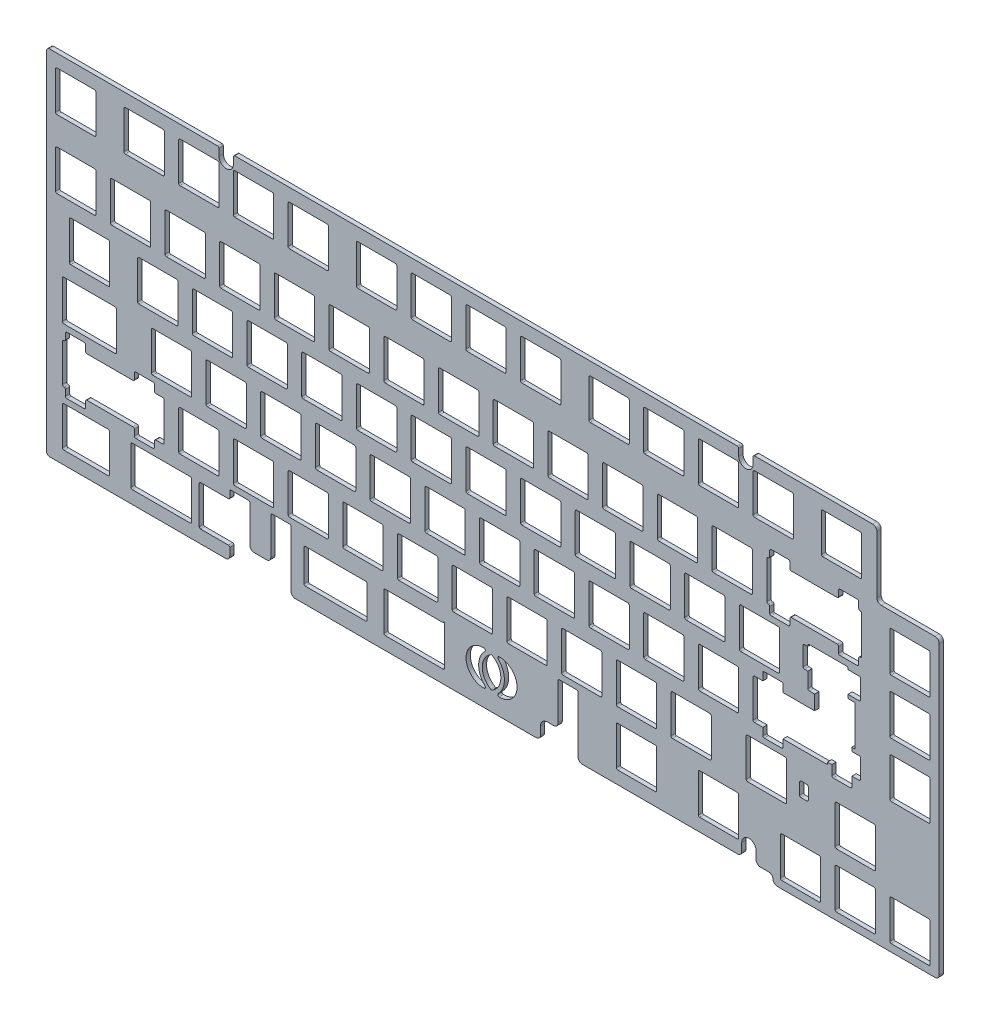
SolidWorks part; units mm, degrees
material "POM Acetal Copolymer"
ref_plane "Front Plane" through (0, 0, 0) normal (0, 0, 1) x (1, 0, 0)
ref_plane "Top Plane" through (0, 0, 0) normal (0, 1, 0) x (1, 0, 0)
ref_plane "Right Plane" through (0, 0, 0) normal (1, 0, 0) x (0, 0, -1)
sketch "Model" plane through (0, 0, 0) normal (0, 0, 1) x (1, 0, 0)
  line L0 (274.4928, 83.607) -> (287.4928, 83.607)
  line L1 (273.9928, 70.107) -> (273.9928, 75.3421)
  line L2 (8.8553, 129.8695) -> (8.8553, 63.082)
  line L3 (67.4518, 130.9695) -> (9.9553, 130.9695)
  line L4 (319.7678, 63.082) -> (319.7678, 106.4532)
  line L5 (195.4959, 7.957) -> (249.4928, 7.957)
  line L6 (86.9959, 28.958) -> (86.9959, 16.157)
  line L7 (187.4959, 29.458) -> (193.4959, 29.458)
  line L8 (193.9959, 28.958) -> (193.9959, 9.457)
  line L9 (186.9959, 16.157) -> (186.9959, 28.958)
  line L10 (87.4959, 29.458) -> (93.4959, 29.458)
  line L11 (126.357, 12.957) -> (126.357, 25.957)
  line L12 (62.0594, 12.957) -> (62.0594, 25.957)
  line L13 (38.2454, 12.957) -> (38.2454, 25.957)
  line L14 (14.4343, 12.957) -> (14.4343, 25.957)
  line L15 (72.207, 12.457) -> (62.5594, 12.457)
  line L16 (62.5594, 26.457) -> (72.207, 26.457)
  line L17 (59.3945, 25.957) -> (59.3945, 12.957)
  line L18 (58.8945, 12.457) -> (38.7454, 12.457)
  line L19 (38.7454, 26.457) -> (58.8945, 26.457)
  line L20 (30.8195, 25.957) -> (30.8195, 12.957)
  line L21 (30.3195, 12.457) -> (14.9343, 12.457)
  line L22 (14.9343, 26.457) -> (30.3195, 26.457)
  line L23 (93.9959, 28.958) -> (93.9959, 9.457)
  line L24 (146.9959, 12.457) -> (126.857, 12.457)
  line L25 (126.857, 26.457) -> (146.9959, 26.457)
  line L26 (147.4959, 26.7823) -> (147.4959, 12.957)
  line L27 (9.9553, 7.957) -> (71.207, 7.957)
  line L28 (95.4959, 7.957) -> (179.3625, 7.957)
  line L29 (263.3678, 5.0945) -> (318.2678, 5.0945)
  line L30 (180.8625, 12.157) -> (180.8625, 9.457)
  line L31 (250.9928, 12.157) -> (250.9928, 9.457)
  line L32 (255.9928, 12.157) -> (255.9928, 9.457)
  line L33 (183.3625, 14.657) -> (185.4959, 14.657)
  line L34 (81.207, 14.657) -> (85.4959, 14.657)
  line L35 (257.4928, 7.957) -> (260.371, 7.957)
  line L36 (8.8553, 63.082) -> (8.8553, 9.057)
  line L37 (319.7678, 63.082) -> (319.7678, 6.5945)
  line L38 (75.4518, 130.9695) -> (248.4268, 130.9695)
  line L39 (256.4268, 130.9695) -> (296.5553, 130.9695)
  line L40 (298.0553, 129.4695) -> (298.0553, 109.4532)
  line L41 (299.5553, 107.9532) -> (318.2678, 107.9532)
  line L42 (271.6572, 41.007) -> (273.6572, 41.007)
  line L43 (274.1572, 40.507) -> (274.1572, 36.507)
  line L44 (273.6572, 36.007) -> (271.6572, 36.007)
  line L45 (271.1572, 36.507) -> (271.1572, 40.507)
  line L46 (260.7295, 105.157) -> (260.7295, 103.157)
  line L47 (268.2295, 102.657) -> (284.2295, 102.657)
  line L48 (268.2295, 88.657) -> (284.2295, 88.657)
  line L49 (261.2295, 105.657) -> (267.2295, 105.657)
  line L50 (261.2295, 85.657) -> (267.2295, 85.657)
  line L51 (267.7295, 103.157) -> (267.7295, 105.157)
  line L52 (267.7295, 88.157) -> (267.7295, 86.157)
  line L53 (291.7295, 105.157) -> (291.7295, 103.157)
  line L54 (291.2295, 105.657) -> (285.2295, 105.657)
  line L55 (291.2295, 85.657) -> (285.2295, 85.657)
  line L56 (284.7295, 103.157) -> (284.7295, 105.157)
  line L57 (284.7295, 88.157) -> (284.7295, 86.157)
  line L58 (258.3508, 50.557) -> (258.3508, 48.057)
  line L59 (265.3508, 50.557) -> (280.8516, 50.557)
  line L60 (258.8508, 67.557) -> (264.8508, 67.557)
  line L61 (258.8508, 47.557) -> (264.8508, 47.557)
  line L62 (265.3508, 64.557) -> (265.3508, 67.057)
  line L63 (265.3508, 50.557) -> (265.3508, 48.057)
  line L64 (288.8508, 47.557) -> (282.8508, 47.557)
  line L65 (282.3508, 51.3421) -> (282.3508, 48.057)
  line L66 (15.4632, 48.0073) -> (15.4632, 46.007)
  line L67 (22.9632, 45.5073) -> (38.9632, 45.5073)
  line L68 (22.9632, 31.5073) -> (38.9632, 31.5073)
  line L69 (15.9632, 48.5073) -> (21.9632, 48.5073)
  line L70 (15.9632, 28.5073) -> (21.9632, 28.5073)
  line L71 (22.4632, 46.0073) -> (22.4632, 48.0073)
  line L72 (22.4632, 31.0073) -> (22.4632, 29.0073)
  line L73 (46.4632, 48.0073) -> (46.4632, 46.007)
  line L74 (45.9632, 48.5073) -> (39.9632, 48.5073)
  line L75 (45.9632, 28.5073) -> (39.9632, 28.5073)
  line L76 (39.4632, 46.0073) -> (39.4632, 48.0073)
  line L77 (39.4632, 31.0073) -> (39.4632, 29.0073)
  line L78 (258.3508, 50.557) -> (255.4453, 50.557)
  line L79 (276.3765, 69.607) -> (274.4928, 69.607)
  line L80 (276.3765, 64.557) -> (276.3765, 69.607)
  line L81 (292.3508, 82.2801) -> (292.3508, 75.8421)
  line L82 (292.3508, 58.2801) -> (292.3508, 51.8421)
  line L83 (291.8508, 82.7801) -> (287.9953, 82.7801)
  line L84 (255.4453, 64.557) -> (258.3508, 64.557)
  line L85 (290.3765, 74.0611) -> (290.3765, 60.0611)
  line L86 (254.9453, 64.057) -> (254.9453, 51.057)
  line L87 (287.9953, 75.3421) -> (291.8508, 75.3421)
  line L88 (289.3508, 58.7801) -> (291.8508, 58.7801)
  line L89 (290.3765, 74.0611) -> (287.9953, 74.0611)
  line L90 (287.9953, 74.0611) -> (287.9953, 75.3421)
  line L91 (289.3508, 58.7801) -> (289.3508, 60.0611)
  line L92 (289.3508, 60.0611) -> (290.3765, 60.0611)
  line L93 (282.3508, 51.3421) -> (280.8516, 51.3421)
  line L94 (280.8516, 51.3421) -> (280.8516, 50.557)
  line L95 (258.3508, 67.057) -> (258.3508, 64.557)
  line L96 (289.3508, 48.057) -> (289.3508, 51.3421)
  line L97 (291.8508, 51.3421) -> (289.3508, 51.3421)
  line L98 (287.9928, 83.107) -> (287.9953, 82.7801)
  line L99 (265.3508, 64.557) -> (276.3765, 64.557)
  line L100 (272.3508, 82.2801) -> (272.3508, 75.8421)
  line L101 (272.8508, 82.7801) -> (273.9928, 82.7801)
  line L102 (273.9928, 75.3421) -> (272.8508, 75.3421)
  line L103 (273.9928, 82.7801) -> (273.9928, 83.107)
  line L104 (259.7053, 89.157) -> (259.7053, 102.157)
  line L105 (292.7553, 102.157) -> (292.7553, 89.157)
  line L106 (291.7295, 86.157) -> (291.7295, 88.157)
  line L107 (292.2295, 88.657) -> (292.2553, 88.657)
  line L108 (292.2295, 102.657) -> (292.2553, 102.657)
  line L109 (260.2053, 102.657) -> (260.2295, 102.657)
  line L110 (260.7295, 86.157) -> (260.7295, 88.157)
  line L111 (260.2295, 88.657) -> (260.2053, 88.657)
  line L112 (49.8678, 45.007) -> (49.8678, 32.007)
  line L113 (46.4632, 29.0073) -> (46.4632, 31.007)
  line L114 (46.9632, 31.507) -> (49.3678, 31.507)
  line L115 (46.9632, 45.507) -> (49.3678, 45.507)
  line L116 (14.4365, 32.007) -> (14.4365, 45.007)
  line L117 (15.4632, 29.0073) -> (15.4632, 31.007)
  line L118 (14.9632, 31.507) -> (14.9365, 31.507)
  line L119 (14.9365, 45.507) -> (14.9632, 45.507)
  line L120 (79.707, 28.958) -> (79.707, 16.157)
  line L121 (72.707, 11.957) -> (72.707, 9.457)
  line L122 (72.707, 26.957) -> (72.707, 28.958)
  line L123 (73.207, 29.458) -> (79.207, 29.458)
  line L124 (120.5413, 13.957) -> (120.5413, 24.957)
  line L125 (99.0413, 13.457) -> (120.0413, 13.457)
  line L126 (98.5413, 24.957) -> (98.5413, 13.957)
  line L127 (120.0413, 25.457) -> (99.0413, 25.457)
  line L144 (12.5303, 112.4445) -> (25.5803, 112.4445)
  line L145 (26.0803, 112.9445) -> (26.0803, 125.9945)
  line L146 (25.5803, 126.4945) -> (12.5303, 126.4945)
  line L147 (12.0303, 125.9945) -> (12.0303, 112.9445)
  line L148 (36.3428, 112.4445) -> (49.3928, 112.4445)
  line L149 (49.8928, 112.9445) -> (49.8928, 125.9945)
  line L150 (49.3928, 126.4945) -> (36.3428, 126.4945)
  line L151 (35.8428, 125.9945) -> (35.8428, 112.9445)
  line L152 (93.4928, 112.4445) -> (106.5428, 112.4445)
  line L153 (107.0428, 112.9445) -> (107.0428, 125.9945)
  line L154 (106.5428, 126.4945) -> (93.4928, 126.4945)
  line L155 (92.9928, 125.9945) -> (92.9928, 112.9445)
  line L156 (117.3053, 112.4445) -> (130.3553, 112.4445)
  line L157 (130.8553, 112.9445) -> (130.8553, 125.9945)
  line L158 (130.3553, 126.4945) -> (117.3053, 126.4945)
  line L159 (116.8053, 125.9945) -> (116.8053, 112.9445)
  line L160 (136.3553, 112.4445) -> (149.4053, 112.4445)
  line L161 (149.9053, 112.9445) -> (149.9053, 125.9945)
  line L162 (149.4053, 126.4945) -> (136.3553, 126.4945)
  line L163 (135.8553, 125.9945) -> (135.8553, 112.9445)
  line L164 (155.4053, 112.4445) -> (168.4553, 112.4445)
  line L165 (168.9553, 112.9445) -> (168.9553, 125.9945)
  line L166 (168.4553, 126.4945) -> (155.4053, 126.4945)
  line L167 (154.9053, 125.9945) -> (154.9053, 112.9445)
  line L168 (174.4553, 112.4445) -> (187.5053, 112.4445)
  line L169 (188.0053, 112.9445) -> (188.0053, 125.9945)
  line L170 (187.5053, 126.4945) -> (174.4553, 126.4945)
  line L171 (173.9553, 125.9945) -> (173.9553, 112.9445)
  line L172 (198.2678, 112.4445) -> (211.3178, 112.4445)
  line L173 (211.8178, 112.9445) -> (211.8178, 125.9945)
  line L174 (211.3178, 126.4945) -> (198.2678, 126.4945)
  line L175 (197.7678, 125.9945) -> (197.7678, 112.9445)
  line L176 (217.3178, 112.4445) -> (230.3678, 112.4445)
  line L177 (230.8678, 112.9445) -> (230.8678, 125.9945)
  line L178 (230.3678, 126.4945) -> (217.3178, 126.4945)
  line L179 (216.8178, 125.9945) -> (216.8178, 112.9445)
  line L180 (279.2303, 112.4445) -> (292.2803, 112.4445)
  line L181 (292.7803, 112.9445) -> (292.7803, 125.9945)
  line L182 (292.2803, 126.4945) -> (279.2303, 126.4945)
  line L183 (278.7303, 125.9945) -> (278.7303, 112.9445)
  line L184 (303.0428, 88.632) -> (316.0928, 88.632)
  line L185 (316.5928, 89.132) -> (316.5928, 102.182)
  line L186 (316.0928, 102.682) -> (303.0428, 102.682)
  line L187 (302.5428, 102.182) -> (302.5428, 89.132)
  line L188 (283.9928, 26.7195) -> (297.0428, 26.7195)
  line L189 (297.5428, 27.2195) -> (297.5428, 40.2695)
  line L190 (297.0428, 40.7695) -> (283.9928, 40.7695)
  line L191 (283.4928, 40.2695) -> (283.4928, 27.2195)
  line L192 (303.0428, 7.6695) -> (316.0928, 7.6695)
  line L193 (316.5928, 8.1695) -> (316.5928, 21.2195)
  line L194 (316.0928, 21.7195) -> (303.0428, 21.7195)
  line L195 (302.5428, 21.2195) -> (302.5428, 8.1695)
  line L196 (283.9928, 7.6695) -> (297.0428, 7.6695)
  line L197 (297.5428, 8.1695) -> (297.5428, 21.2195)
  line L198 (297.0428, 21.7195) -> (283.9928, 21.7195)
  line L199 (283.4928, 21.2195) -> (283.4928, 8.1695)
  line L200 (264.9428, 7.6695) -> (277.9928, 7.6695)
  line L201 (278.4928, 8.1695) -> (278.4928, 21.2195)
  line L202 (277.9928, 21.7195) -> (264.9428, 21.7195)
  line L203 (264.4428, 21.2195) -> (264.4428, 8.1695)
  line L204 (236.3678, 12.432) -> (249.4178, 12.432)
  line L205 (249.9178, 12.932) -> (249.9178, 25.982)
  line L206 (249.4178, 26.482) -> (236.3678, 26.482)
  line L207 (235.8678, 25.982) -> (235.8678, 12.932)
  line L208 (207.7928, 12.432) -> (220.8428, 12.432)
  line L209 (221.3428, 12.932) -> (221.3428, 25.982)
  line L210 (220.8428, 26.482) -> (207.7928, 26.482)
  line L211 (207.2928, 25.982) -> (207.2928, 12.932)
  line L212 (253.0365, 31.482) -> (266.0865, 31.482)
  line L213 (266.5865, 31.982) -> (266.5865, 45.032)
  line L214 (266.0865, 45.532) -> (253.0365, 45.532)
  line L215 (252.5365, 45.032) -> (252.5365, 31.982)
  line L216 (226.8428, 31.482) -> (239.8928, 31.482)
  line L217 (240.3928, 31.982) -> (240.3928, 45.032)
  line L218 (239.8928, 45.532) -> (226.8428, 45.532)
  line L219 (226.3428, 45.032) -> (226.3428, 31.982)
  line L220 (207.7928, 31.482) -> (220.8428, 31.482)
  line L221 (221.3428, 31.982) -> (221.3428, 45.032)
  line L222 (220.8428, 45.532) -> (207.7928, 45.532)
  line L223 (207.2928, 45.032) -> (207.2928, 31.982)
  line L224 (188.7428, 31.482) -> (201.7928, 31.482)
  line L225 (202.2928, 31.982) -> (202.2928, 45.032)
  line L226 (201.7928, 45.532) -> (188.7428, 45.532)
  line L227 (188.2428, 45.032) -> (188.2428, 31.982)
  line L228 (169.6928, 31.482) -> (182.7428, 31.482)
  line L229 (183.2428, 31.982) -> (183.2428, 45.032)
  line L230 (182.7428, 45.532) -> (169.6928, 45.532)
  line L231 (169.1928, 45.032) -> (169.1928, 31.982)
  line L232 (150.6428, 31.482) -> (163.6928, 31.482)
  line L233 (164.1928, 31.982) -> (164.1928, 45.032)
  line L234 (163.6928, 45.532) -> (150.6428, 45.532)
  line L235 (150.1428, 45.032) -> (150.1428, 31.982)
  line L236 (131.5928, 31.482) -> (144.6428, 31.482)
  line L237 (145.1428, 31.982) -> (145.1428, 45.032)
  line L238 (144.6428, 45.532) -> (131.5928, 45.532)
  line L239 (131.0928, 45.032) -> (131.0928, 31.982)
  line L240 (112.5428, 31.482) -> (125.5928, 31.482)
  line L241 (126.0928, 31.982) -> (126.0928, 45.032)
  line L242 (125.5928, 45.532) -> (112.5428, 45.532)
  line L243 (112.0428, 45.032) -> (112.0428, 31.982)
  line L244 (93.4928, 31.482) -> (106.5428, 31.482)
  line L245 (107.0428, 31.982) -> (107.0428, 45.032)
  line L246 (106.5428, 45.532) -> (93.4928, 45.532)
  line L247 (92.9928, 45.032) -> (92.9928, 31.982)
  line L248 (74.4428, 31.482) -> (87.4928, 31.482)
  line L249 (87.9928, 31.982) -> (87.9928, 45.032)
  line L250 (87.4928, 45.532) -> (74.4428, 45.532)
  line L251 (73.9428, 45.032) -> (73.9428, 31.982)
  line L252 (55.3928, 31.482) -> (68.4428, 31.482)
  line L253 (68.9428, 31.982) -> (68.9428, 45.032)
  line L254 (68.4428, 45.532) -> (55.3928, 45.532)
  line L255 (54.8928, 45.032) -> (54.8928, 31.982)
  line L256 (45.8678, 50.532) -> (58.9178, 50.532)
  line L257 (59.4178, 51.032) -> (59.4178, 64.082)
  line L258 (58.9178, 64.582) -> (45.8678, 64.582)
  line L259 (45.3678, 64.082) -> (45.3678, 51.032)
  line L260 (64.9178, 50.532) -> (77.9678, 50.532)
  line L261 (78.4678, 51.032) -> (78.4678, 64.082)
  line L262 (77.9678, 64.582) -> (64.9178, 64.582)
  line L263 (64.4178, 64.082) -> (64.4178, 51.032)
  line L264 (83.9678, 50.532) -> (97.0178, 50.532)
  line L265 (97.5178, 51.032) -> (97.5178, 64.082)
  line L266 (97.0178, 64.582) -> (83.9678, 64.582)
  line L267 (83.4678, 64.082) -> (83.4678, 51.032)
  line L268 (103.0178, 50.532) -> (116.0678, 50.532)
  line L269 (116.5678, 51.032) -> (116.5678, 64.082)
  line L270 (116.0678, 64.582) -> (103.0178, 64.582)
  line L271 (102.5178, 64.082) -> (102.5178, 51.032)
  line L272 (122.0678, 50.532) -> (135.1178, 50.532)
  line L273 (135.6178, 51.032) -> (135.6178, 64.082)
  line L274 (135.1178, 64.582) -> (122.0678, 64.582)
  line L275 (121.5678, 64.082) -> (121.5678, 51.032)
  line L276 (141.1178, 50.532) -> (154.1678, 50.532)
  line L277 (154.6678, 51.032) -> (154.6678, 64.082)
  line L278 (154.1678, 64.582) -> (141.1178, 64.582)
  line L279 (140.6178, 64.082) -> (140.6178, 51.032)
  line L280 (160.1678, 50.532) -> (173.2178, 50.532)
  line L281 (173.7178, 51.032) -> (173.7178, 64.082)
  line L282 (173.2178, 64.582) -> (160.1678, 64.582)
  line L283 (159.6678, 64.082) -> (159.6678, 51.032)
  line L284 (179.2178, 50.532) -> (192.2678, 50.532)
  line L285 (192.7678, 51.032) -> (192.7678, 64.082)
  line L286 (192.2678, 64.582) -> (179.2178, 64.582)
  line L287 (178.7178, 64.082) -> (178.7178, 51.032)
  line L288 (198.2678, 50.532) -> (211.3178, 50.532)
  line L289 (211.8178, 51.032) -> (211.8178, 64.082)
  line L290 (211.3178, 64.582) -> (198.2678, 64.582)
  line L291 (197.7678, 64.082) -> (197.7678, 51.032)
  line L292 (217.3178, 50.532) -> (230.3678, 50.532)
  line L293 (230.8678, 51.032) -> (230.8678, 64.082)
  line L294 (230.3678, 64.582) -> (217.3178, 64.582)
  line L295 (216.8178, 64.082) -> (216.8178, 51.032)
  line L296 (236.3678, 50.532) -> (249.4178, 50.532)
  line L297 (249.9178, 51.032) -> (249.9178, 64.082)
  line L298 (249.4178, 64.582) -> (236.3678, 64.582)
  line L299 (235.8678, 64.082) -> (235.8678, 51.032)
  line L300 (17.2928, 69.582) -> (30.3428, 69.582)
  line L301 (30.8428, 70.082) -> (30.8428, 83.132)
  line L302 (30.3428, 83.632) -> (17.2928, 83.632)
  line L303 (16.7928, 83.132) -> (16.7928, 70.082)
  line L304 (12.5303, 88.632) -> (25.5803, 88.632)
  line L305 (26.0803, 89.132) -> (26.0803, 102.182)
  line L306 (25.5803, 102.682) -> (12.5303, 102.682)
  line L307 (12.0303, 102.182) -> (12.0303, 89.132)
  line L308 (31.5803, 88.632) -> (44.6303, 88.632)
  line L309 (45.1303, 89.132) -> (45.1303, 102.182)
  line L310 (44.6303, 102.682) -> (31.5803, 102.682)
  line L311 (31.0803, 102.182) -> (31.0803, 89.132)
  line L312 (50.6303, 88.632) -> (63.6803, 88.632)
  line L313 (64.1803, 89.132) -> (64.1803, 102.182)
  line L314 (63.6803, 102.682) -> (50.6303, 102.682)
  line L315 (50.1303, 102.182) -> (50.1303, 89.132)
  line L316 (69.6803, 88.632) -> (82.7303, 88.632)
  line L317 (83.2303, 89.132) -> (83.2303, 102.182)
  line L318 (82.7303, 102.682) -> (69.6803, 102.682)
  line L319 (69.1803, 102.182) -> (69.1803, 89.132)
  line L320 (88.7303, 88.632) -> (101.7803, 88.632)
  line L321 (102.2803, 89.132) -> (102.2803, 102.182)
  line L322 (101.7803, 102.682) -> (88.7303, 102.682)
  line L323 (88.2303, 102.182) -> (88.2303, 89.132)
  line L324 (107.7803, 88.632) -> (120.8303, 88.632)
  line L325 (121.3303, 89.132) -> (121.3303, 102.182)
  line L326 (120.8303, 102.682) -> (107.7803, 102.682)
  line L327 (107.2803, 102.182) -> (107.2803, 89.132)
  line L328 (126.8303, 88.632) -> (139.8803, 88.632)
  line L329 (140.3803, 89.132) -> (140.3803, 102.182)
  line L330 (139.8803, 102.682) -> (126.8303, 102.682)
  line L331 (126.3303, 102.182) -> (126.3303, 89.132)
  line L332 (145.8803, 88.632) -> (158.9303, 88.632)
  line L333 (159.4303, 89.132) -> (159.4303, 102.182)
  line L334 (158.9303, 102.682) -> (145.8803, 102.682)
  line L335 (145.3803, 102.182) -> (145.3803, 89.132)
  line L336 (164.9303, 88.632) -> (177.9803, 88.632)
  line L337 (178.4803, 89.132) -> (178.4803, 102.182)
  line L338 (177.9803, 102.682) -> (164.9303, 102.682)
  line L339 (164.4303, 102.182) -> (164.4303, 89.132)
  line L340 (183.9803, 88.632) -> (197.0303, 88.632)
  line L341 (197.5303, 89.132) -> (197.5303, 102.182)
  line L342 (197.0303, 102.682) -> (183.9803, 102.682)
  line L343 (183.4803, 102.182) -> (183.4803, 89.132)
  line L344 (203.0303, 88.632) -> (216.0803, 88.632)
  line L345 (216.5803, 89.132) -> (216.5803, 102.182)
  line L346 (216.0803, 102.682) -> (203.0303, 102.682)
  line L347 (202.5303, 102.182) -> (202.5303, 89.132)
  line L348 (222.0803, 88.632) -> (235.1303, 88.632)
  line L349 (235.6303, 89.132) -> (235.6303, 102.182)
  line L350 (235.1303, 102.682) -> (222.0803, 102.682)
  line L351 (221.5803, 102.182) -> (221.5803, 89.132)
  line L352 (241.1303, 88.632) -> (254.1803, 88.632)
  line L353 (254.6803, 89.132) -> (254.6803, 102.182)
  line L354 (254.1803, 102.682) -> (241.1303, 102.682)
  line L355 (240.6303, 102.182) -> (240.6303, 89.132)
  line L356 (41.1053, 69.582) -> (54.1553, 69.582)
  line L357 (54.6553, 70.082) -> (54.6553, 83.132)
  line L358 (54.1553, 83.632) -> (41.1053, 83.632)
  line L359 (40.6053, 83.132) -> (40.6053, 70.082)
  line L360 (60.1553, 69.582) -> (73.2053, 69.582)
  line L361 (73.7053, 70.082) -> (73.7053, 83.132)
  line L362 (73.2053, 83.632) -> (60.1553, 83.632)
  line L363 (59.6553, 83.132) -> (59.6553, 70.082)
  line L364 (79.2053, 69.582) -> (92.2553, 69.582)
  line L365 (92.7553, 70.082) -> (92.7553, 83.132)
  line L366 (92.2553, 83.632) -> (79.2053, 83.632)
  line L367 (78.7053, 83.132) -> (78.7053, 70.082)
  line L368 (98.2553, 69.582) -> (111.3053, 69.582)
  line L369 (111.8053, 70.082) -> (111.8053, 83.132)
  line L370 (111.3053, 83.632) -> (98.2553, 83.632)
  line L371 (97.7553, 83.132) -> (97.7553, 70.082)
  line L372 (117.3053, 69.582) -> (130.3553, 69.582)
  line L373 (130.8553, 70.082) -> (130.8553, 83.132)
  line L374 (130.3553, 83.632) -> (117.3053, 83.632)
  line L375 (116.8053, 83.132) -> (116.8053, 70.082)
  line L376 (136.3553, 69.582) -> (149.4053, 69.582)
  line L377 (149.9053, 70.082) -> (149.9053, 83.132)
  line L378 (149.4053, 83.632) -> (136.3553, 83.632)
  line L379 (135.8553, 83.132) -> (135.8553, 70.082)
  line L380 (155.4053, 69.582) -> (168.4553, 69.582)
  line L381 (168.9553, 70.082) -> (168.9553, 83.132)
  line L382 (168.4553, 83.632) -> (155.4053, 83.632)
  line L383 (154.9053, 83.132) -> (154.9053, 70.082)
  line L384 (174.4553, 69.582) -> (187.5053, 69.582)
  line L385 (188.0053, 70.082) -> (188.0053, 83.132)
  line L386 (187.5053, 83.632) -> (174.4553, 83.632)
  line L387 (173.9553, 83.132) -> (173.9553, 70.082)
  line L388 (193.5053, 69.582) -> (206.5553, 69.582)
  line L389 (207.0553, 70.082) -> (207.0553, 83.132)
  line L390 (206.5553, 83.632) -> (193.5053, 83.632)
  line L391 (193.0053, 83.132) -> (193.0053, 70.082)
  line L392 (212.5553, 69.582) -> (225.6053, 69.582)
  line L393 (226.1053, 70.082) -> (226.1053, 83.132)
  line L394 (225.6053, 83.632) -> (212.5553, 83.632)
  line L395 (212.0553, 83.132) -> (212.0553, 70.082)
  line L396 (231.6053, 69.582) -> (244.6553, 69.582)
  line L397 (245.1553, 70.082) -> (245.1553, 83.132)
  line L398 (244.6553, 83.632) -> (231.6053, 83.632)
  line L399 (231.1053, 83.132) -> (231.1053, 70.082)
  line L400 (250.6553, 69.582) -> (263.7053, 69.582)
  line L401 (264.2053, 70.082) -> (264.2053, 83.132)
  line L402 (263.7053, 83.632) -> (250.6553, 83.632)
  line L403 (250.1553, 83.132) -> (250.1553, 70.082)
  line L404 (303.0428, 69.582) -> (316.0928, 69.582)
  line L405 (316.5928, 70.082) -> (316.5928, 83.132)
  line L406 (316.0928, 83.632) -> (303.0428, 83.632)
  line L407 (302.5428, 83.132) -> (302.5428, 70.082)
  line L408 (303.0678, 64.582) -> (316.1178, 64.582)
  line L409 (302.5428, 51.057) -> (302.5428, 64.057)
  line L410 (316.0678, 50.532) -> (303.0678, 50.532)
  line L411 (316.5928, 64.107) -> (316.5928, 51.057)
  line L412 (32.699, 50.507) -> (14.9365, 50.507)
  line L413 (33.249, 64.057) -> (33.249, 51.057)
  line L414 (14.9365, 64.607) -> (32.699, 64.607)
  line L415 (14.3865, 51.057) -> (14.3865, 64.057)
  line L416 (236.3678, 112.4445) -> (249.4178, 112.4445)
  line L417 (249.9178, 112.9445) -> (249.9178, 125.9945)
  line L418 (249.4178, 126.4945) -> (236.3678, 126.4945)
  line L419 (235.8678, 125.9945) -> (235.8678, 112.9445)
  line L420 (255.4178, 112.4445) -> (268.4678, 112.4445)
  line L421 (268.9678, 112.9445) -> (268.9678, 125.9945)
  line L422 (268.4678, 126.4945) -> (255.4178, 126.4945)
  line L423 (254.9178, 125.9945) -> (254.9178, 112.9445)
  line L424 (55.3928, 112.4445) -> (68.4428, 112.4445)
  line L425 (68.9428, 112.9445) -> (68.9428, 125.9945)
  line L426 (68.4428, 126.4945) -> (55.3928, 126.4945)
  line L427 (54.8928, 125.9945) -> (54.8928, 112.9445)
  line L428 (74.4428, 112.4445) -> (87.4928, 112.4445)
  line L429 (87.9928, 112.9445) -> (87.9928, 125.9945)
  line L430 (87.4928, 126.4945) -> (74.4428, 126.4945)
  line L431 (73.9428, 125.9945) -> (73.9428, 112.9445)
  line L432 (67.4518, 130.9695) -> (75.4518, 130.9695)
  line L433 (248.4268, 130.9695) -> (256.4268, 130.9695)
  arc A0 (319.7678, 106.4532) -> (318.2678, 107.9532) centre (318.2678, 106.4532) ccw
  arc A1 (318.2678, 5.0945) -> (319.7678, 6.5945) centre (318.2678, 6.5945) ccw
  arc A2 (193.9959, 9.457) -> (195.4959, 7.957) centre (195.4959, 9.457) ccw
  arc A3 (273.9928, 70.107) -> (274.4928, 69.607) centre (274.4928, 70.107) ccw
  arc A4 (287.9928, 83.107) -> (287.4928, 83.607) centre (287.4928, 83.107) ccw
  arc A5 (274.4928, 83.607) -> (273.9928, 83.107) centre (274.4928, 83.107) ccw
  arc A6 (8.8553, 9.057) -> (9.9553, 7.957) centre (9.9553, 9.057) ccw
  arc A7 (9.9553, 130.9695) -> (8.8553, 129.8695) centre (9.9553, 129.8695) ccw
  arc A8 (85.4959, 14.657) -> (86.9959, 16.157) centre (85.4959, 16.157) ccw
  arc A9 (193.9959, 28.958) -> (193.4959, 29.458) centre (193.4959, 28.958) ccw
  arc A10 (187.4959, 29.458) -> (186.9959, 28.958) centre (187.4959, 28.958) ccw
  arc A11 (185.4959, 14.657) -> (186.9959, 16.157) centre (185.4959, 16.157) ccw
  arc A12 (87.4959, 29.458) -> (86.9959, 28.958) centre (87.4959, 28.958) ccw
  arc A13 (126.357, 12.957) -> (126.857, 12.457) centre (126.857, 12.957) ccw
  arc A14 (93.9959, 28.958) -> (93.4959, 29.458) centre (93.4959, 28.958) ccw
  arc A15 (38.7454, 26.457) -> (38.2454, 25.957) centre (38.7454, 25.957) ccw
  arc A16 (14.9343, 26.457) -> (14.4343, 25.957) centre (14.9343, 25.957) ccw
  arc A17 (62.0594, 12.957) -> (62.5594, 12.457) centre (62.5594, 12.957) ccw
  arc A18 (62.5594, 26.457) -> (62.0594, 25.957) centre (62.5594, 25.957) ccw
  arc A19 (38.2454, 12.957) -> (38.7454, 12.457) centre (38.7454, 12.957) ccw
  arc A20 (58.8945, 12.457) -> (59.3945, 12.957) centre (58.8945, 12.957) ccw
  arc A21 (59.3945, 25.957) -> (58.8945, 26.457) centre (58.8945, 25.957) ccw
  arc A22 (30.3195, 12.457) -> (30.8195, 12.957) centre (30.3195, 12.957) ccw
  arc A23 (14.4343, 12.957) -> (14.9343, 12.457) centre (14.9343, 12.957) ccw
  arc A24 (30.8195, 25.957) -> (30.3195, 26.457) centre (30.3195, 25.957) ccw
  arc A25 (126.857, 26.457) -> (126.357, 25.957) centre (126.857, 25.957) ccw
  arc A26 (146.9959, 12.457) -> (147.4959, 12.957) centre (146.9959, 12.957) ccw
  arc A27 (147.4959, 26.7823) -> (146.9959, 26.457) centre (147.4647, 26.2833) ccw
  arc A28 (93.9959, 9.457) -> (95.4959, 7.957) centre (95.4959, 9.457) ccw
  arc A29 (261.8694, 6.5258) -> (263.3678, 5.0945) centre (263.3678, 6.5945) ccw
  arc A30 (261.8694, 6.5258) -> (260.371, 7.957) centre (260.371, 6.457) ccw
  arc A31 (179.3625, 7.957) -> (180.8625, 9.457) centre (179.3625, 9.457) ccw
  arc A32 (255.9928, 9.457) -> (257.4928, 7.957) centre (257.4928, 9.457) ccw
  arc A33 (249.4928, 7.957) -> (250.9928, 9.457) centre (249.4928, 9.457) ccw
  arc A34 (255.9928, 12.157) -> (250.9928, 12.157) centre (253.4928, 12.157) ccw
  arc A35 (183.3625, 14.657) -> (180.8625, 12.157) centre (183.3625, 12.157) ccw
  arc A36 (298.0553, 129.4695) -> (296.5553, 130.9695) centre (296.5553, 129.4695) ccw
  arc A37 (298.0553, 109.4532) -> (299.5553, 107.9532) centre (299.5553, 109.4532) ccw
  arc A38 (271.6572, 41.007) -> (271.1572, 40.507) centre (271.6572, 40.507) ccw
  arc A39 (274.1572, 40.507) -> (273.6572, 41.007) centre (273.6572, 40.507) ccw
  arc A40 (273.6572, 36.007) -> (274.1572, 36.507) centre (273.6572, 36.507) ccw
  arc A41 (271.1572, 36.507) -> (271.6572, 36.007) centre (271.6572, 36.507) ccw
  arc A42 (260.2295, 102.657) -> (260.7295, 103.157) centre (260.2295, 103.157) ccw
  arc A43 (267.7295, 103.157) -> (268.2295, 102.657) centre (268.2295, 103.157) ccw
  arc A44 (261.2295, 105.657) -> (260.7295, 105.157) centre (261.2295, 105.157) ccw
  arc A45 (260.7295, 86.157) -> (261.2295, 85.657) centre (261.2295, 86.157) ccw
  arc A46 (267.7295, 105.157) -> (267.2295, 105.657) centre (267.2295, 105.157) ccw
  arc A47 (268.2295, 88.657) -> (267.7295, 88.157) centre (268.2295, 88.157) ccw
  arc A48 (267.2295, 85.657) -> (267.7295, 86.157) centre (267.2295, 86.157) ccw
  arc A49 (284.2295, 102.657) -> (284.7295, 103.157) centre (284.2295, 103.157) ccw
  arc A50 (291.7295, 105.157) -> (291.2295, 105.657) centre (291.2295, 105.157) ccw
  arc A51 (291.2295, 85.657) -> (291.7295, 86.157) centre (291.2295, 86.157) ccw
  arc A52 (285.2295, 105.657) -> (284.7295, 105.157) centre (285.2295, 105.157) ccw
  arc A53 (284.7295, 88.157) -> (284.2295, 88.657) centre (284.2295, 88.157) ccw
  arc A54 (284.7295, 86.157) -> (285.2295, 85.657) centre (285.2295, 86.157) ccw
  arc A55 (258.8508, 67.557) -> (258.3508, 67.057) centre (258.8508, 67.057) ccw
  arc A56 (258.3508, 48.057) -> (258.8508, 47.557) centre (258.8508, 48.057) ccw
  arc A57 (265.3508, 67.057) -> (264.8508, 67.557) centre (264.8508, 67.057) ccw
  arc A58 (264.8508, 47.557) -> (265.3508, 48.057) centre (264.8508, 48.057) ccw
  arc A59 (288.8508, 47.557) -> (289.3508, 48.057) centre (288.8508, 48.057) ccw
  arc A60 (282.3508, 48.057) -> (282.8508, 47.557) centre (282.8508, 48.057) ccw
  arc A61 (14.9632, 45.507) -> (15.4632, 46.007) centre (14.9632, 46.007) ccw
  arc A62 (22.4632, 46.0073) -> (22.9632, 45.5073) centre (22.9632, 46.0073) ccw
  arc A63 (15.9632, 48.5073) -> (15.4632, 48.0073) centre (15.9632, 48.0073) ccw
  arc A64 (15.4632, 29.0073) -> (15.9632, 28.5073) centre (15.9632, 29.0073) ccw
  arc A65 (22.4632, 48.0073) -> (21.9632, 48.5073) centre (21.9632, 48.0073) ccw
  arc A66 (22.9632, 31.5073) -> (22.4632, 31.0073) centre (22.9632, 31.0073) ccw
  arc A67 (21.9632, 28.5073) -> (22.4632, 29.0073) centre (21.9632, 29.0073) ccw
  arc A68 (38.9632, 45.5073) -> (39.4632, 46.0073) centre (38.9632, 46.0073) ccw
  arc A69 (46.4632, 48.0073) -> (45.9632, 48.5073) centre (45.9632, 48.0073) ccw
  arc A70 (45.9632, 28.5073) -> (46.4632, 29.0073) centre (45.9632, 29.0073) ccw
  arc A71 (39.9632, 48.5073) -> (39.4632, 48.0073) centre (39.9632, 48.0073) ccw
  arc A72 (39.4632, 31.0073) -> (38.9632, 31.5073) centre (38.9632, 31.0073) ccw
  arc A73 (39.4632, 29.0073) -> (39.9632, 28.5073) centre (39.9632, 29.0073) ccw
  arc A74 (291.8508, 51.3421) -> (292.3508, 51.8421) centre (291.8508, 51.8421) ccw
  arc A75 (292.3508, 82.2801) -> (291.8508, 82.7801) centre (291.8508, 82.2801) ccw
  arc A76 (292.3508, 58.2801) -> (291.8508, 58.7801) centre (291.8508, 58.2801) ccw
  arc A77 (291.8508, 75.3421) -> (292.3508, 75.8421) centre (291.8508, 75.8421) ccw
  arc A78 (272.8508, 82.7801) -> (272.3508, 82.2801) centre (272.8508, 82.2801) ccw
  arc A79 (272.3508, 75.8421) -> (272.8508, 75.3421) centre (272.8508, 75.8421) ccw
  arc A80 (259.7053, 89.157) -> (260.2053, 88.657) centre (260.2053, 89.157) ccw
  arc A81 (260.2053, 102.657) -> (259.7053, 102.157) centre (260.2053, 102.157) ccw
  arc A82 (292.2553, 88.657) -> (292.7553, 89.157) centre (292.2553, 89.157) ccw
  arc A83 (292.7553, 102.157) -> (292.2553, 102.657) centre (292.2553, 102.157) ccw
  arc A84 (292.2295, 88.657) -> (291.7295, 88.157) centre (292.2295, 88.157) ccw
  arc A85 (291.7295, 103.157) -> (292.2295, 102.657) centre (292.2295, 103.157) ccw
  arc A86 (260.7295, 88.157) -> (260.2295, 88.657) centre (260.2295, 88.157) ccw
  arc A87 (49.3678, 31.507) -> (49.8678, 32.007) centre (49.3678, 32.007) ccw
  arc A88 (49.8678, 45.007) -> (49.3678, 45.507) centre (49.3678, 45.007) ccw
  arc A89 (46.9632, 31.507) -> (46.4632, 31.007) centre (46.9632, 31.007) ccw
  arc A90 (46.4632, 46.007) -> (46.9632, 45.507) centre (46.9632, 46.007) ccw
  arc A91 (14.4365, 32.007) -> (14.9365, 31.507) centre (14.9365, 32.007) ccw
  arc A92 (14.9365, 45.507) -> (14.4365, 45.007) centre (14.9365, 45.007) ccw
  arc A93 (15.4632, 31.007) -> (14.9632, 31.507) centre (14.9632, 31.007) ccw
  arc A94 (72.707, 11.957) -> (72.207, 12.457) centre (72.207, 11.957) ccw
  arc A95 (72.207, 26.457) -> (72.707, 26.957) centre (72.207, 26.957) ccw
  arc A96 (73.207, 29.458) -> (72.707, 28.958) centre (73.207, 28.958) ccw
  arc A97 (79.707, 28.958) -> (79.207, 29.458) centre (79.207, 28.958) ccw
  arc A98 (71.207, 7.957) -> (72.707, 9.457) centre (71.207, 9.457) ccw
  arc A99 (79.707, 16.157) -> (81.207, 14.657) centre (81.207, 16.157) ccw
  arc A100 (255.4453, 64.557) -> (254.9453, 64.057) centre (255.4453, 64.057) ccw
  arc A101 (254.9453, 51.057) -> (255.4453, 50.557) centre (255.4453, 51.057) ccw
  arc A102 (120.0413, 13.457) -> (120.5413, 13.957) centre (120.0413, 13.957) ccw
  arc A103 (98.5413, 13.957) -> (99.0413, 13.457) centre (99.0413, 13.957) ccw
  arc A104 (99.0413, 25.457) -> (98.5413, 24.957) centre (99.0413, 24.957) ccw
  arc A105 (120.5413, 24.957) -> (120.0413, 25.457) centre (120.0413, 24.957) ccw
  circle A106 centre (161.0365, 19.8697) radius 6.0649
  circle A107 centre (166.6822, 19.8697) radius 6.0649
  circle A108 centre (161.0365, 19.8697) radius 7.3149
  circle A109 centre (166.6822, 19.8697) radius 7.3149
  arc A134 (303.0678, 64.582) -> (302.5428, 64.057) centre (303.0678, 64.057) ccw
  arc A135 (302.5428, 51.057) -> (303.0678, 50.532) centre (303.0678, 51.057) ccw
  arc A136 (316.0678, 50.532) -> (316.5928, 51.057) centre (316.0678, 51.057) ccw
  arc A137 (316.5928, 64.107) -> (316.1178, 64.582) centre (316.1178, 64.107) ccw
  arc A138 (14.3865, 51.057) -> (14.9365, 50.507) centre (14.9365, 51.057) ccw
  arc A139 (32.699, 50.507) -> (33.249, 51.057) centre (32.699, 51.057) ccw
  arc A140 (33.249, 64.057) -> (32.699, 64.607) centre (32.699, 64.057) ccw
  arc A141 (14.9365, 64.607) -> (14.3865, 64.057) centre (14.9365, 64.057) ccw
  arc A142 (25.5803, 112.4445) -> (26.0803, 112.9445) centre (25.5803, 112.9445) ccw
  arc A143 (26.0803, 125.9945) -> (25.5803, 126.4945) centre (25.5803, 125.9945) ccw
  arc A144 (12.5303, 126.4945) -> (12.0303, 125.9945) centre (12.5303, 125.9945) ccw
  arc A145 (12.0303, 112.9445) -> (12.5303, 112.4445) centre (12.5303, 112.9445) ccw
  arc A146 (49.3928, 112.4445) -> (49.8928, 112.9445) centre (49.3928, 112.9445) ccw
  arc A147 (49.8928, 125.9945) -> (49.3928, 126.4945) centre (49.3928, 125.9945) ccw
  arc A148 (36.3428, 126.4945) -> (35.8428, 125.9945) centre (36.3428, 125.9945) ccw
  arc A149 (35.8428, 112.9445) -> (36.3428, 112.4445) centre (36.3428, 112.9445) ccw
  arc A150 (106.5428, 112.4445) -> (107.0428, 112.9445) centre (106.5428, 112.9445) ccw
  arc A151 (107.0428, 125.9945) -> (106.5428, 126.4945) centre (106.5428, 125.9945) ccw
  arc A152 (93.4928, 126.4945) -> (92.9928, 125.9945) centre (93.4928, 125.9945) ccw
  arc A153 (92.9928, 112.9445) -> (93.4928, 112.4445) centre (93.4928, 112.9445) ccw
  arc A154 (130.3553, 112.4445) -> (130.8553, 112.9445) centre (130.3553, 112.9445) ccw
  arc A155 (130.8553, 125.9945) -> (130.3553, 126.4945) centre (130.3553, 125.9945) ccw
  arc A156 (117.3053, 126.4945) -> (116.8053, 125.9945) centre (117.3053, 125.9945) ccw
  arc A157 (116.8053, 112.9445) -> (117.3053, 112.4445) centre (117.3053, 112.9445) ccw
  arc A158 (149.4053, 112.4445) -> (149.9053, 112.9445) centre (149.4053, 112.9445) ccw
  arc A159 (149.9053, 125.9945) -> (149.4053, 126.4945) centre (149.4053, 125.9945) ccw
  arc A160 (136.3553, 126.4945) -> (135.8553, 125.9945) centre (136.3553, 125.9945) ccw
  arc A161 (135.8553, 112.9445) -> (136.3553, 112.4445) centre (136.3553, 112.9445) ccw
  arc A162 (168.4553, 112.4445) -> (168.9553, 112.9445) centre (168.4553, 112.9445) ccw
  arc A163 (168.9553, 125.9945) -> (168.4553, 126.4945) centre (168.4553, 125.9945) ccw
  arc A164 (155.4053, 126.4945) -> (154.9053, 125.9945) centre (155.4053, 125.9945) ccw
  arc A165 (154.9053, 112.9445) -> (155.4053, 112.4445) centre (155.4053, 112.9445) ccw
  arc A166 (187.5053, 112.4445) -> (188.0053, 112.9445) centre (187.5053, 112.9445) ccw
  arc A167 (188.0053, 125.9945) -> (187.5053, 126.4945) centre (187.5053, 125.9945) ccw
  arc A168 (174.4553, 126.4945) -> (173.9553, 125.9945) centre (174.4553, 125.9945) ccw
  arc A169 (173.9553, 112.9445) -> (174.4553, 112.4445) centre (174.4553, 112.9445) ccw
  arc A170 (211.3178, 112.4445) -> (211.8178, 112.9445) centre (211.3178, 112.9445) ccw
  arc A171 (211.8178, 125.9945) -> (211.3178, 126.4945) centre (211.3178, 125.9945) ccw
  arc A172 (198.2678, 126.4945) -> (197.7678, 125.9945) centre (198.2678, 125.9945) ccw
  arc A173 (197.7678, 112.9445) -> (198.2678, 112.4445) centre (198.2678, 112.9445) ccw
  arc A174 (230.3678, 112.4445) -> (230.8678, 112.9445) centre (230.3678, 112.9445) ccw
  arc A175 (230.8678, 125.9945) -> (230.3678, 126.4945) centre (230.3678, 125.9945) ccw
  arc A176 (217.3178, 126.4945) -> (216.8178, 125.9945) centre (217.3178, 125.9945) ccw
  arc A177 (216.8178, 112.9445) -> (217.3178, 112.4445) centre (217.3178, 112.9445) ccw
  arc A178 (292.2803, 112.4445) -> (292.7803, 112.9445) centre (292.2803, 112.9445) ccw
  arc A179 (292.7803, 125.9945) -> (292.2803, 126.4945) centre (292.2803, 125.9945) ccw
  arc A180 (279.2303, 126.4945) -> (278.7303, 125.9945) centre (279.2303, 125.9945) ccw
  arc A181 (278.7303, 112.9445) -> (279.2303, 112.4445) centre (279.2303, 112.9445) ccw
  arc A182 (316.0928, 88.632) -> (316.5928, 89.132) centre (316.0928, 89.132) ccw
  arc A183 (316.5928, 102.182) -> (316.0928, 102.682) centre (316.0928, 102.182) ccw
  arc A184 (303.0428, 102.682) -> (302.5428, 102.182) centre (303.0428, 102.182) ccw
  arc A185 (302.5428, 89.132) -> (303.0428, 88.632) centre (303.0428, 89.132) ccw
  arc A186 (297.0428, 26.7195) -> (297.5428, 27.2195) centre (297.0428, 27.2195) ccw
  arc A187 (297.5428, 40.2695) -> (297.0428, 40.7695) centre (297.0428, 40.2695) ccw
  arc A188 (283.9928, 40.7695) -> (283.4928, 40.2695) centre (283.9928, 40.2695) ccw
  arc A189 (283.4928, 27.2195) -> (283.9928, 26.7195) centre (283.9928, 27.2195) ccw
  arc A190 (316.0928, 7.6695) -> (316.5928, 8.1695) centre (316.0928, 8.1695) ccw
  arc A191 (316.5928, 21.2195) -> (316.0928, 21.7195) centre (316.0928, 21.2195) ccw
  arc A192 (303.0428, 21.7195) -> (302.5428, 21.2195) centre (303.0428, 21.2195) ccw
  arc A193 (302.5428, 8.1695) -> (303.0428, 7.6695) centre (303.0428, 8.1695) ccw
  arc A194 (297.0428, 7.6695) -> (297.5428, 8.1695) centre (297.0428, 8.1695) ccw
  arc A195 (297.5428, 21.2195) -> (297.0428, 21.7195) centre (297.0428, 21.2195) ccw
  arc A196 (283.9928, 21.7195) -> (283.4928, 21.2195) centre (283.9928, 21.2195) ccw
  arc A197 (283.4928, 8.1695) -> (283.9928, 7.6695) centre (283.9928, 8.1695) ccw
  arc A198 (277.9928, 7.6695) -> (278.4928, 8.1695) centre (277.9928, 8.1695) ccw
  arc A199 (278.4928, 21.2195) -> (277.9928, 21.7195) centre (277.9928, 21.2195) ccw
  arc A200 (264.9428, 21.7195) -> (264.4428, 21.2195) centre (264.9428, 21.2195) ccw
  arc A201 (264.4428, 8.1695) -> (264.9428, 7.6695) centre (264.9428, 8.1695) ccw
  arc A202 (249.4178, 12.432) -> (249.9178, 12.932) centre (249.4178, 12.932) ccw
  arc A203 (249.9178, 25.982) -> (249.4178, 26.482) centre (249.4178, 25.982) ccw
  arc A204 (236.3678, 26.482) -> (235.8678, 25.982) centre (236.3678, 25.982) ccw
  arc A205 (235.8678, 12.932) -> (236.3678, 12.432) centre (236.3678, 12.932) ccw
  arc A206 (220.8428, 12.432) -> (221.3428, 12.932) centre (220.8428, 12.932) ccw
  arc A207 (221.3428, 25.982) -> (220.8428, 26.482) centre (220.8428, 25.982) ccw
  arc A208 (207.7928, 26.482) -> (207.2928, 25.982) centre (207.7928, 25.982) ccw
  arc A209 (207.2928, 12.932) -> (207.7928, 12.432) centre (207.7928, 12.932) ccw
  arc A210 (266.0865, 31.482) -> (266.5865, 31.982) centre (266.0865, 31.982) ccw
  arc A211 (266.5865, 45.032) -> (266.0865, 45.532) centre (266.0865, 45.032) ccw
  arc A212 (253.0365, 45.532) -> (252.5365, 45.032) centre (253.0365, 45.032) ccw
  arc A213 (252.5365, 31.982) -> (253.0365, 31.482) centre (253.0365, 31.982) ccw
  arc A214 (239.8928, 31.482) -> (240.3928, 31.982) centre (239.8928, 31.982) ccw
  arc A215 (240.3928, 45.032) -> (239.8928, 45.532) centre (239.8928, 45.032) ccw
  arc A216 (226.8428, 45.532) -> (226.3428, 45.032) centre (226.8428, 45.032) ccw
  arc A217 (226.3428, 31.982) -> (226.8428, 31.482) centre (226.8428, 31.982) ccw
  arc A218 (220.8428, 31.482) -> (221.3428, 31.982) centre (220.8428, 31.982) ccw
  arc A219 (221.3428, 45.032) -> (220.8428, 45.532) centre (220.8428, 45.032) ccw
  arc A220 (207.7928, 45.532) -> (207.2928, 45.032) centre (207.7928, 45.032) ccw
  arc A221 (207.2928, 31.982) -> (207.7928, 31.482) centre (207.7928, 31.982) ccw
  arc A222 (201.7928, 31.482) -> (202.2928, 31.982) centre (201.7928, 31.982) ccw
  arc A223 (202.2928, 45.032) -> (201.7928, 45.532) centre (201.7928, 45.032) ccw
  arc A224 (188.7428, 45.532) -> (188.2428, 45.032) centre (188.7428, 45.032) ccw
  arc A225 (188.2428, 31.982) -> (188.7428, 31.482) centre (188.7428, 31.982) ccw
  arc A226 (182.7428, 31.482) -> (183.2428, 31.982) centre (182.7428, 31.982) ccw
  arc A227 (183.2428, 45.032) -> (182.7428, 45.532) centre (182.7428, 45.032) ccw
  arc A228 (169.6928, 45.532) -> (169.1928, 45.032) centre (169.6928, 45.032) ccw
  arc A229 (169.1928, 31.982) -> (169.6928, 31.482) centre (169.6928, 31.982) ccw
  arc A230 (163.6928, 31.482) -> (164.1928, 31.982) centre (163.6928, 31.982) ccw
  arc A231 (164.1928, 45.032) -> (163.6928, 45.532) centre (163.6928, 45.032) ccw
  arc A232 (150.6428, 45.532) -> (150.1428, 45.032) centre (150.6428, 45.032) ccw
  arc A233 (150.1428, 31.982) -> (150.6428, 31.482) centre (150.6428, 31.982) ccw
  arc A234 (144.6428, 31.482) -> (145.1428, 31.982) centre (144.6428, 31.982) ccw
  arc A235 (145.1428, 45.032) -> (144.6428, 45.532) centre (144.6428, 45.032) ccw
  arc A236 (131.5928, 45.532) -> (131.0928, 45.032) centre (131.5928, 45.032) ccw
  arc A237 (131.0928, 31.982) -> (131.5928, 31.482) centre (131.5928, 31.982) ccw
  arc A238 (125.5928, 31.482) -> (126.0928, 31.982) centre (125.5928, 31.982) ccw
  arc A239 (126.0928, 45.032) -> (125.5928, 45.532) centre (125.5928, 45.032) ccw
  arc A240 (112.5428, 45.532) -> (112.0428, 45.032) centre (112.5428, 45.032) ccw
  arc A241 (112.0428, 31.982) -> (112.5428, 31.482) centre (112.5428, 31.982) ccw
  arc A242 (106.5428, 31.482) -> (107.0428, 31.982) centre (106.5428, 31.982) ccw
  arc A243 (107.0428, 45.032) -> (106.5428, 45.532) centre (106.5428, 45.032) ccw
  arc A244 (93.4928, 45.532) -> (92.9928, 45.032) centre (93.4928, 45.032) ccw
  arc A245 (92.9928, 31.982) -> (93.4928, 31.482) centre (93.4928, 31.982) ccw
  arc A246 (87.4928, 31.482) -> (87.9928, 31.982) centre (87.4928, 31.982) ccw
  arc A247 (87.9928, 45.032) -> (87.4928, 45.532) centre (87.4928, 45.032) ccw
  arc A248 (74.4428, 45.532) -> (73.9428, 45.032) centre (74.4428, 45.032) ccw
  arc A249 (73.9428, 31.982) -> (74.4428, 31.482) centre (74.4428, 31.982) ccw
  arc A250 (68.4428, 31.482) -> (68.9428, 31.982) centre (68.4428, 31.982) ccw
  arc A251 (68.9428, 45.032) -> (68.4428, 45.532) centre (68.4428, 45.032) ccw
  arc A252 (55.3928, 45.532) -> (54.8928, 45.032) centre (55.3928, 45.032) ccw
  arc A253 (54.8928, 31.982) -> (55.3928, 31.482) centre (55.3928, 31.982) ccw
  arc A254 (58.9178, 50.532) -> (59.4178, 51.032) centre (58.9178, 51.032) ccw
  arc A255 (59.4178, 64.082) -> (58.9178, 64.582) centre (58.9178, 64.082) ccw
  arc A256 (45.8678, 64.582) -> (45.3678, 64.082) centre (45.8678, 64.082) ccw
  arc A257 (45.3678, 51.032) -> (45.8678, 50.532) centre (45.8678, 51.032) ccw
  arc A258 (77.9678, 50.532) -> (78.4678, 51.032) centre (77.9678, 51.032) ccw
  arc A259 (78.4678, 64.082) -> (77.9678, 64.582) centre (77.9678, 64.082) ccw
  arc A260 (64.9178, 64.582) -> (64.4178, 64.082) centre (64.9178, 64.082) ccw
  arc A261 (64.4178, 51.032) -> (64.9178, 50.532) centre (64.9178, 51.032) ccw
  arc A262 (97.0178, 50.532) -> (97.5178, 51.032) centre (97.0178, 51.032) ccw
  arc A263 (97.5178, 64.082) -> (97.0178, 64.582) centre (97.0178, 64.082) ccw
  arc A264 (83.9678, 64.582) -> (83.4678, 64.082) centre (83.9678, 64.082) ccw
  arc A265 (83.4678, 51.032) -> (83.9678, 50.532) centre (83.9678, 51.032) ccw
  arc A266 (116.0678, 50.532) -> (116.5678, 51.032) centre (116.0678, 51.032) ccw
  arc A267 (116.5678, 64.082) -> (116.0678, 64.582) centre (116.0678, 64.082) ccw
  arc A268 (103.0178, 64.582) -> (102.5178, 64.082) centre (103.0178, 64.082) ccw
  arc A269 (102.5178, 51.032) -> (103.0178, 50.532) centre (103.0178, 51.032) ccw
  arc A270 (135.1178, 50.532) -> (135.6178, 51.032) centre (135.1178, 51.032) ccw
  arc A271 (135.6178, 64.082) -> (135.1178, 64.582) centre (135.1178, 64.082) ccw
  arc A272 (122.0678, 64.582) -> (121.5678, 64.082) centre (122.0678, 64.082) ccw
  arc A273 (121.5678, 51.032) -> (122.0678, 50.532) centre (122.0678, 51.032) ccw
  arc A274 (154.1678, 50.532) -> (154.6678, 51.032) centre (154.1678, 51.032) ccw
  arc A275 (154.6678, 64.082) -> (154.1678, 64.582) centre (154.1678, 64.082) ccw
  arc A276 (141.1178, 64.582) -> (140.6178, 64.082) centre (141.1178, 64.082) ccw
  arc A277 (140.6178, 51.032) -> (141.1178, 50.532) centre (141.1178, 51.032) ccw
  arc A278 (173.2178, 50.532) -> (173.7178, 51.032) centre (173.2178, 51.032) ccw
  arc A279 (173.7178, 64.082) -> (173.2178, 64.582) centre (173.2178, 64.082) ccw
  arc A280 (160.1678, 64.582) -> (159.6678, 64.082) centre (160.1678, 64.082) ccw
  arc A281 (159.6678, 51.032) -> (160.1678, 50.532) centre (160.1678, 51.032) ccw
  arc A282 (192.2678, 50.532) -> (192.7678, 51.032) centre (192.2678, 51.032) ccw
  arc A283 (192.7678, 64.082) -> (192.2678, 64.582) centre (192.2678, 64.082) ccw
  arc A284 (179.2178, 64.582) -> (178.7178, 64.082) centre (179.2178, 64.082) ccw
  arc A285 (178.7178, 51.032) -> (179.2178, 50.532) centre (179.2178, 51.032) ccw
  arc A286 (211.3178, 50.532) -> (211.8178, 51.032) centre (211.3178, 51.032) ccw
  arc A287 (211.8178, 64.082) -> (211.3178, 64.582) centre (211.3178, 64.082) ccw
  arc A288 (198.2678, 64.582) -> (197.7678, 64.082) centre (198.2678, 64.082) ccw
  arc A289 (197.7678, 51.032) -> (198.2678, 50.532) centre (198.2678, 51.032) ccw
  arc A290 (230.3678, 50.532) -> (230.8678, 51.032) centre (230.3678, 51.032) ccw
  arc A291 (230.8678, 64.082) -> (230.3678, 64.582) centre (230.3678, 64.082) ccw
  arc A292 (217.3178, 64.582) -> (216.8178, 64.082) centre (217.3178, 64.082) ccw
  arc A293 (216.8178, 51.032) -> (217.3178, 50.532) centre (217.3178, 51.032) ccw
  arc A294 (249.4178, 50.532) -> (249.9178, 51.032) centre (249.4178, 51.032) ccw
  arc A295 (249.9178, 64.082) -> (249.4178, 64.582) centre (249.4178, 64.082) ccw
  arc A296 (236.3678, 64.582) -> (235.8678, 64.082) centre (236.3678, 64.082) ccw
  arc A297 (235.8678, 51.032) -> (236.3678, 50.532) centre (236.3678, 51.032) ccw
  arc A298 (30.3428, 69.582) -> (30.8428, 70.082) centre (30.3428, 70.082) ccw
  arc A299 (30.8428, 83.132) -> (30.3428, 83.632) centre (30.3428, 83.132) ccw
  arc A300 (17.2928, 83.632) -> (16.7928, 83.132) centre (17.2928, 83.132) ccw
  arc A301 (16.7928, 70.082) -> (17.2928, 69.582) centre (17.2928, 70.082) ccw
  arc A302 (25.5803, 88.632) -> (26.0803, 89.132) centre (25.5803, 89.132) ccw
  arc A303 (26.0803, 102.182) -> (25.5803, 102.682) centre (25.5803, 102.182) ccw
  arc A304 (12.5303, 102.682) -> (12.0303, 102.182) centre (12.5303, 102.182) ccw
  arc A305 (12.0303, 89.132) -> (12.5303, 88.632) centre (12.5303, 89.132) ccw
  arc A306 (44.6303, 88.632) -> (45.1303, 89.132) centre (44.6303, 89.132) ccw
  arc A307 (45.1303, 102.182) -> (44.6303, 102.682) centre (44.6303, 102.182) ccw
  arc A308 (31.5803, 102.682) -> (31.0803, 102.182) centre (31.5803, 102.182) ccw
  arc A309 (31.0803, 89.132) -> (31.5803, 88.632) centre (31.5803, 89.132) ccw
  arc A310 (63.6803, 88.632) -> (64.1803, 89.132) centre (63.6803, 89.132) ccw
  arc A311 (64.1803, 102.182) -> (63.6803, 102.682) centre (63.6803, 102.182) ccw
  arc A312 (50.6303, 102.682) -> (50.1303, 102.182) centre (50.6303, 102.182) ccw
  arc A313 (50.1303, 89.132) -> (50.6303, 88.632) centre (50.6303, 89.132) ccw
  arc A314 (82.7303, 88.632) -> (83.2303, 89.132) centre (82.7303, 89.132) ccw
  arc A315 (83.2303, 102.182) -> (82.7303, 102.682) centre (82.7303, 102.182) ccw
  arc A316 (69.6803, 102.682) -> (69.1803, 102.182) centre (69.6803, 102.182) ccw
  arc A317 (69.1803, 89.132) -> (69.6803, 88.632) centre (69.6803, 89.132) ccw
  arc A318 (101.7803, 88.632) -> (102.2803, 89.132) centre (101.7803, 89.132) ccw
  arc A319 (102.2803, 102.182) -> (101.7803, 102.682) centre (101.7803, 102.182) ccw
  arc A320 (88.7303, 102.682) -> (88.2303, 102.182) centre (88.7303, 102.182) ccw
  arc A321 (88.2303, 89.132) -> (88.7303, 88.632) centre (88.7303, 89.132) ccw
  arc A322 (120.8303, 88.632) -> (121.3303, 89.132) centre (120.8303, 89.132) ccw
  arc A323 (121.3303, 102.182) -> (120.8303, 102.682) centre (120.8303, 102.182) ccw
  arc A324 (107.7803, 102.682) -> (107.2803, 102.182) centre (107.7803, 102.182) ccw
  arc A325 (107.2803, 89.132) -> (107.7803, 88.632) centre (107.7803, 89.132) ccw
  arc A326 (139.8803, 88.632) -> (140.3803, 89.132) centre (139.8803, 89.132) ccw
  arc A327 (140.3803, 102.182) -> (139.8803, 102.682) centre (139.8803, 102.182) ccw
  arc A328 (126.8303, 102.682) -> (126.3303, 102.182) centre (126.8303, 102.182) ccw
  arc A329 (126.3303, 89.132) -> (126.8303, 88.632) centre (126.8303, 89.132) ccw
  arc A330 (158.9303, 88.632) -> (159.4303, 89.132) centre (158.9303, 89.132) ccw
  arc A331 (159.4303, 102.182) -> (158.9303, 102.682) centre (158.9303, 102.182) ccw
  arc A332 (145.8803, 102.682) -> (145.3803, 102.182) centre (145.8803, 102.182) ccw
  arc A333 (145.3803, 89.132) -> (145.8803, 88.632) centre (145.8803, 89.132) ccw
  arc A334 (177.9803, 88.632) -> (178.4803, 89.132) centre (177.9803, 89.132) ccw
  arc A335 (178.4803, 102.182) -> (177.9803, 102.682) centre (177.9803, 102.182) ccw
  arc A336 (164.9303, 102.682) -> (164.4303, 102.182) centre (164.9303, 102.182) ccw
  arc A337 (164.4303, 89.132) -> (164.9303, 88.632) centre (164.9303, 89.132) ccw
  arc A338 (197.0303, 88.632) -> (197.5303, 89.132) centre (197.0303, 89.132) ccw
  arc A339 (197.5303, 102.182) -> (197.0303, 102.682) centre (197.0303, 102.182) ccw
  arc A340 (183.9803, 102.682) -> (183.4803, 102.182) centre (183.9803, 102.182) ccw
  arc A341 (183.4803, 89.132) -> (183.9803, 88.632) centre (183.9803, 89.132) ccw
  arc A342 (216.0803, 88.632) -> (216.5803, 89.132) centre (216.0803, 89.132) ccw
  arc A343 (216.5803, 102.182) -> (216.0803, 102.682) centre (216.0803, 102.182) ccw
  arc A344 (203.0303, 102.682) -> (202.5303, 102.182) centre (203.0303, 102.182) ccw
  arc A345 (202.5303, 89.132) -> (203.0303, 88.632) centre (203.0303, 89.132) ccw
  arc A346 (235.1303, 88.632) -> (235.6303, 89.132) centre (235.1303, 89.132) ccw
  arc A347 (235.6303, 102.182) -> (235.1303, 102.682) centre (235.1303, 102.182) ccw
  arc A348 (222.0803, 102.682) -> (221.5803, 102.182) centre (222.0803, 102.182) ccw
  arc A349 (221.5803, 89.132) -> (222.0803, 88.632) centre (222.0803, 89.132) ccw
  arc A350 (254.1803, 88.632) -> (254.6803, 89.132) centre (254.1803, 89.132) ccw
  arc A351 (254.6803, 102.182) -> (254.1803, 102.682) centre (254.1803, 102.182) ccw
  arc A352 (241.1303, 102.682) -> (240.6303, 102.182) centre (241.1303, 102.182) ccw
  arc A353 (240.6303, 89.132) -> (241.1303, 88.632) centre (241.1303, 89.132) ccw
  arc A354 (54.1553, 69.582) -> (54.6553, 70.082) centre (54.1553, 70.082) ccw
  arc A355 (54.6553, 83.132) -> (54.1553, 83.632) centre (54.1553, 83.132) ccw
  arc A356 (41.1053, 83.632) -> (40.6053, 83.132) centre (41.1053, 83.132) ccw
  arc A357 (40.6053, 70.082) -> (41.1053, 69.582) centre (41.1053, 70.082) ccw
  arc A358 (73.2053, 69.582) -> (73.7053, 70.082) centre (73.2053, 70.082) ccw
  arc A359 (73.7053, 83.132) -> (73.2053, 83.632) centre (73.2053, 83.132) ccw
  arc A360 (60.1553, 83.632) -> (59.6553, 83.132) centre (60.1553, 83.132) ccw
  arc A361 (59.6553, 70.082) -> (60.1553, 69.582) centre (60.1553, 70.082) ccw
  arc A362 (92.2553, 69.582) -> (92.7553, 70.082) centre (92.2553, 70.082) ccw
  arc A363 (92.7553, 83.132) -> (92.2553, 83.632) centre (92.2553, 83.132) ccw
  arc A364 (79.2053, 83.632) -> (78.7053, 83.132) centre (79.2053, 83.132) ccw
  arc A365 (78.7053, 70.082) -> (79.2053, 69.582) centre (79.2053, 70.082) ccw
  arc A366 (111.3053, 69.582) -> (111.8053, 70.082) centre (111.3053, 70.082) ccw
  arc A367 (111.8053, 83.132) -> (111.3053, 83.632) centre (111.3053, 83.132) ccw
  arc A368 (98.2553, 83.632) -> (97.7553, 83.132) centre (98.2553, 83.132) ccw
  arc A369 (97.7553, 70.082) -> (98.2553, 69.582) centre (98.2553, 70.082) ccw
  arc A370 (130.3553, 69.582) -> (130.8553, 70.082) centre (130.3553, 70.082) ccw
  arc A371 (130.8553, 83.132) -> (130.3553, 83.632) centre (130.3553, 83.132) ccw
  arc A372 (117.3053, 83.632) -> (116.8053, 83.132) centre (117.3053, 83.132) ccw
  arc A373 (116.8053, 70.082) -> (117.3053, 69.582) centre (117.3053, 70.082) ccw
  arc A374 (149.4053, 69.582) -> (149.9053, 70.082) centre (149.4053, 70.082) ccw
  arc A375 (149.9053, 83.132) -> (149.4053, 83.632) centre (149.4053, 83.132) ccw
  arc A376 (136.3553, 83.632) -> (135.8553, 83.132) centre (136.3553, 83.132) ccw
  arc A377 (135.8553, 70.082) -> (136.3553, 69.582) centre (136.3553, 70.082) ccw
  arc A378 (168.4553, 69.582) -> (168.9553, 70.082) centre (168.4553, 70.082) ccw
  arc A379 (168.9553, 83.132) -> (168.4553, 83.632) centre (168.4553, 83.132) ccw
  arc A380 (155.4053, 83.632) -> (154.9053, 83.132) centre (155.4053, 83.132) ccw
  arc A381 (154.9053, 70.082) -> (155.4053, 69.582) centre (155.4053, 70.082) ccw
  arc A382 (187.5053, 69.582) -> (188.0053, 70.082) centre (187.5053, 70.082) ccw
  arc A383 (188.0053, 83.132) -> (187.5053, 83.632) centre (187.5053, 83.132) ccw
  arc A384 (174.4553, 83.632) -> (173.9553, 83.132) centre (174.4553, 83.132) ccw
  arc A385 (173.9553, 70.082) -> (174.4553, 69.582) centre (174.4553, 70.082) ccw
  arc A386 (206.5553, 69.582) -> (207.0553, 70.082) centre (206.5553, 70.082) ccw
  arc A387 (207.0553, 83.132) -> (206.5553, 83.632) centre (206.5553, 83.132) ccw
  arc A388 (193.5053, 83.632) -> (193.0053, 83.132) centre (193.5053, 83.132) ccw
  arc A389 (193.0053, 70.082) -> (193.5053, 69.582) centre (193.5053, 70.082) ccw
  arc A390 (225.6053, 69.582) -> (226.1053, 70.082) centre (225.6053, 70.082) ccw
  arc A391 (226.1053, 83.132) -> (225.6053, 83.632) centre (225.6053, 83.132) ccw
  arc A392 (212.5553, 83.632) -> (212.0553, 83.132) centre (212.5553, 83.132) ccw
  arc A393 (212.0553, 70.082) -> (212.5553, 69.582) centre (212.5553, 70.082) ccw
  arc A394 (244.6553, 69.582) -> (245.1553, 70.082) centre (244.6553, 70.082) ccw
  arc A395 (245.1553, 83.132) -> (244.6553, 83.632) centre (244.6553, 83.132) ccw
  arc A396 (231.6053, 83.632) -> (231.1053, 83.132) centre (231.6053, 83.132) ccw
  arc A397 (231.1053, 70.082) -> (231.6053, 69.582) centre (231.6053, 70.082) ccw
  arc A398 (263.7053, 69.582) -> (264.2053, 70.082) centre (263.7053, 70.082) ccw
  arc A399 (264.2053, 83.132) -> (263.7053, 83.632) centre (263.7053, 83.132) ccw
  arc A400 (250.6553, 83.632) -> (250.1553, 83.132) centre (250.6553, 83.132) ccw
  arc A401 (250.1553, 70.082) -> (250.6553, 69.582) centre (250.6553, 70.082) ccw
  arc A402 (316.0928, 69.582) -> (316.5928, 70.082) centre (316.0928, 70.082) ccw
  arc A403 (316.5928, 83.132) -> (316.0928, 83.632) centre (316.0928, 83.132) ccw
  arc A404 (303.0428, 83.632) -> (302.5428, 83.132) centre (303.0428, 83.132) ccw
  arc A405 (302.5428, 70.082) -> (303.0428, 69.582) centre (303.0428, 70.082) ccw
  arc A406 (249.4178, 112.4445) -> (249.9178, 112.9445) centre (249.4178, 112.9445) ccw
  arc A407 (249.9178, 125.9945) -> (249.4178, 126.4945) centre (249.4178, 125.9945) ccw
  arc A408 (236.3678, 126.4945) -> (235.8678, 125.9945) centre (236.3678, 125.9945) ccw
  arc A409 (235.8678, 112.9445) -> (236.3678, 112.4445) centre (236.3678, 112.9445) ccw
  arc A410 (268.4678, 112.4445) -> (268.9678, 112.9445) centre (268.4678, 112.9445) ccw
  arc A411 (268.9678, 125.9945) -> (268.4678, 126.4945) centre (268.4678, 125.9945) ccw
  arc A412 (255.4178, 126.4945) -> (254.9178, 125.9945) centre (255.4178, 125.9945) ccw
  arc A413 (254.9178, 112.9445) -> (255.4178, 112.4445) centre (255.4178, 112.9445) ccw
  arc A414 (68.4428, 112.4445) -> (68.9428, 112.9445) centre (68.4428, 112.9445) ccw
  arc A415 (68.9428, 125.9945) -> (68.4428, 126.4945) centre (68.4428, 125.9945) ccw
  arc A416 (55.3928, 126.4945) -> (54.8928, 125.9945) centre (55.3928, 125.9945) ccw
  arc A417 (54.8928, 112.9445) -> (55.3928, 112.4445) centre (55.3928, 112.9445) ccw
  arc A418 (87.4928, 112.4445) -> (87.9928, 112.9445) centre (87.4928, 112.9445) ccw
  arc A419 (87.9928, 125.9945) -> (87.4928, 126.4945) centre (87.4928, 125.9945) ccw
  arc A420 (74.4428, 126.4945) -> (73.9428, 125.9945) centre (74.4428, 125.9945) ccw
  arc A421 (73.9428, 112.9445) -> (74.4428, 112.4445) centre (74.4428, 112.9445) ccw
  point P323 (147.4959, 19.8697)
  dimension "D1" = 1.25
  dimension "D2" = 1.25
extrude "Boss-Extrude1" add sketch "Model" along normal blind 1.5 contours L120 A99 L34 A8 L6 A12 L10 A14 L23 A28 L28 A31 L30 A35 L33 A11 L9 A10 L7 A9 L8 A2 L5 A33 L31 A34 L32 A32 L35 A30 A29 L29 A1 L37 L4 A0 L41 A37 L40 A36 L39 L433 L38 L432 L3 A7 L2 L36 A6 L27 A98 | A108 A109 A106 A107 | A108 A109 A107 | A106 A109 A108 A107 | A106 A109 A107 | A107 A108 A106 | A109 A108 A106 region at (11.5493, 128.2755, 0) region at (166.3363, 23.0706, 0) region at (160.4907, 19.8697, 0) region at (163.8593, 25.917, 0) region at (163.8593, 13.8223, 0) region at (154.7937, 19.8697, 0) region at (164.7115, 26.3994, 0)
ref_plane "Plane1" through (164.3115, 0, 0) normal (-1, 0, 0) x (0, 0, 1)
split "Split1" trim tools "Plane1" bodies to split 101 resulting bodies 102 103
combine bodies "Combine1" operation type add bodies to combine 102 103
sketch "Sketch1" plane through (0, 0, 1.5) normal (0, 0, 1) x (1, 0, 0)
  line L0 (68.9518, 130.7195) -> (68.9518, 130.9695)
  line L1 (73.9518, 130.7195) -> (73.9518, 130.9695)
  line L2 (254.9268, 130.7195) -> (254.9268, 130.9695)
  line L3 (254.9268, 130.7195) -> (249.9268, 130.7195)
  line L4 (249.9268, 130.7195) -> (249.9268, 128.1033)
  line L5 (254.9268, 128.1033) -> (254.9268, 130.7195)
  line L6 (254.9268, 130.7195) -> (249.9268, 130.7195)
  line L7 (249.9268, 130.7195) -> (249.9268, 128.1033)
  line L8 (254.9268, 128.1033) -> (254.9268, 130.7195)
  line L9 (73.9518, 130.7195) -> (68.9518, 130.7195)
  line L10 (68.9518, 130.7195) -> (68.9518, 128.1033)
  line L11 (73.9518, 128.1033) -> (73.9518, 130.7195)
  line L12 (73.9518, 130.7195) -> (68.9518, 130.7195)
  line L13 (68.9518, 130.7195) -> (68.9518, 128.1033)
  line L14 (73.9518, 128.1033) -> (73.9518, 130.7195)
  line L15 (249.9268, 130.7195) -> (249.9268, 130.9695)
  line L40 (296.5553, 130.9695) -> (9.9553, 130.9695)
  line L41 (8.8553, 129.8695) -> (8.8553, 9.057)
  line L42 (9.9553, 7.957) -> (71.207, 7.957)
  line L43 (72.707, 9.457) -> (72.707, 11.957)
  line L44 (72.207, 12.457) -> (62.5594, 12.457)
  line L45 (62.0594, 12.957) -> (62.0594, 25.957)
  line L46 (62.5594, 26.457) -> (72.207, 26.457)
  line L47 (72.707, 26.957) -> (72.707, 28.958)
  line L48 (73.207, 29.458) -> (79.207, 29.458)
  line L49 (79.707, 28.958) -> (79.707, 16.157)
  line L50 (81.207, 14.657) -> (85.4959, 14.657)
  line L51 (86.9959, 16.157) -> (86.9959, 28.958)
  line L52 (87.4959, 29.458) -> (93.4959, 29.458)
  line L53 (93.9959, 28.958) -> (93.9959, 9.457)
  line L54 (95.4959, 7.957) -> (179.3625, 7.957)
  line L55 (180.8625, 9.457) -> (180.8625, 12.157)
  line L56 (183.3625, 14.657) -> (185.4959, 14.657)
  line L57 (186.9959, 16.157) -> (186.9959, 28.958)
  line L58 (187.4959, 29.458) -> (193.4959, 29.458)
  line L59 (193.9959, 28.958) -> (193.9959, 9.457)
  line L60 (195.4959, 7.957) -> (249.4928, 7.957)
  line L61 (250.9928, 9.457) -> (250.9928, 12.157)
  line L62 (255.9928, 12.157) -> (255.9928, 9.457)
  line L63 (257.4928, 7.957) -> (260.371, 7.957)
  line L64 (263.3678, 5.0945) -> (318.2678, 5.0945)
  line L65 (319.7678, 6.5945) -> (319.7678, 106.4532)
  line L66 (318.2678, 107.9532) -> (299.5553, 107.9532)
  line L67 (298.0553, 109.4532) -> (298.0553, 129.4695)
  line L68 (296.5553, 130.9695) -> (9.9553, 130.9695)
  line L69 (8.8553, 129.8695) -> (8.8553, 9.057)
  line L70 (9.9553, 7.957) -> (71.207, 7.957)
  line L71 (72.707, 9.457) -> (72.707, 11.957)
  line L72 (72.207, 12.457) -> (62.5594, 12.457)
  line L73 (62.0594, 12.957) -> (62.0594, 25.957)
  line L74 (62.5594, 26.457) -> (72.207, 26.457)
  line L75 (72.707, 26.957) -> (72.707, 28.958)
  line L76 (73.207, 29.458) -> (79.207, 29.458)
  line L77 (79.707, 28.958) -> (79.707, 16.157)
  line L78 (81.207, 14.657) -> (85.4959, 14.657)
  line L79 (86.9959, 16.157) -> (86.9959, 28.958)
  line L80 (87.4959, 29.458) -> (93.4959, 29.458)
  line L81 (93.9959, 28.958) -> (93.9959, 9.457)
  line L82 (95.4959, 7.957) -> (179.3625, 7.957)
  line L83 (180.8625, 9.457) -> (180.8625, 12.157)
  line L84 (183.3625, 14.657) -> (185.4959, 14.657)
  line L85 (186.9959, 16.157) -> (186.9959, 28.958)
  line L86 (187.4959, 29.458) -> (193.4959, 29.458)
  line L87 (193.9959, 28.958) -> (193.9959, 9.457)
  line L88 (195.4959, 7.957) -> (249.4928, 7.957)
  line L89 (250.9928, 9.457) -> (250.9928, 12.157)
  line L90 (255.9928, 12.157) -> (255.9928, 9.457)
  line L91 (257.4928, 7.957) -> (260.371, 7.957)
  line L92 (263.3678, 5.0945) -> (318.2678, 5.0945)
  line L93 (319.7678, 6.5945) -> (319.7678, 106.4532)
  line L94 (318.2678, 107.9532) -> (299.5553, 107.9532)
  line L95 (298.0553, 109.4532) -> (298.0553, 129.4695)
  arc A1 (249.9268, 128.1033) -> (254.9268, 128.1033) centre (252.4268, 128.1033) ccw
  arc A2 (249.9268, 128.1033) -> (254.9268, 128.1033) centre (252.4268, 128.1033) ccw
  arc A3 (68.9518, 128.1033) -> (73.9518, 128.1033) centre (71.4518, 128.1033) ccw
  arc A4 (68.9518, 128.1033) -> (73.9518, 128.1033) centre (71.4518, 128.1033) ccw
  arc A33 (298.0553, 129.4695) -> (296.5553, 130.9695) centre (296.5553, 129.4695) ccw
  arc A34 (9.9553, 130.9695) -> (8.8553, 129.8695) centre (9.9553, 129.8695) ccw
  arc A35 (8.8553, 9.057) -> (9.9553, 7.957) centre (9.9553, 9.057) ccw
  arc A36 (71.207, 7.957) -> (72.707, 9.457) centre (71.207, 9.457) ccw
  arc A37 (72.707, 11.957) -> (72.207, 12.457) centre (72.207, 11.957) ccw
  arc A38 (62.0594, 12.957) -> (62.5594, 12.457) centre (62.5594, 12.957) ccw
  arc A39 (62.5594, 26.457) -> (62.0594, 25.957) centre (62.5594, 25.957) ccw
  arc A40 (72.207, 26.457) -> (72.707, 26.957) centre (72.207, 26.957) ccw
  arc A41 (73.207, 29.458) -> (72.707, 28.958) centre (73.207, 28.958) ccw
  arc A42 (79.707, 28.958) -> (79.207, 29.458) centre (79.207, 28.958) ccw
  arc A43 (79.707, 16.157) -> (81.207, 14.657) centre (81.207, 16.157) ccw
  arc A44 (85.4959, 14.657) -> (86.9959, 16.157) centre (85.4959, 16.157) ccw
  arc A45 (87.4959, 29.458) -> (86.9959, 28.958) centre (87.4959, 28.958) ccw
  arc A46 (93.9959, 28.958) -> (93.4959, 29.458) centre (93.4959, 28.958) ccw
  arc A47 (93.9959, 9.457) -> (95.4959, 7.957) centre (95.4959, 9.457) ccw
  arc A48 (179.3625, 7.957) -> (180.8625, 9.457) centre (179.3625, 9.457) ccw
  arc A49 (183.3625, 14.657) -> (180.8625, 12.157) centre (183.3625, 12.157) ccw
  arc A50 (185.4959, 14.657) -> (186.9959, 16.157) centre (185.4959, 16.157) ccw
  arc A51 (187.4959, 29.458) -> (186.9959, 28.958) centre (187.4959, 28.958) ccw
  arc A52 (193.9959, 28.958) -> (193.4959, 29.458) centre (193.4959, 28.958) ccw
  arc A53 (193.9959, 9.457) -> (195.4959, 7.957) centre (195.4959, 9.457) ccw
  arc A54 (249.4928, 7.957) -> (250.9928, 9.457) centre (249.4928, 9.457) ccw
  arc A55 (255.9928, 12.157) -> (250.9928, 12.157) centre (253.4928, 12.157) ccw
  arc A56 (255.9928, 9.457) -> (257.4928, 7.957) centre (257.4928, 9.457) ccw
  arc A57 (261.8694, 6.5258) -> (260.371, 7.957) centre (260.371, 6.457) ccw
  arc A58 (261.8694, 6.5258) -> (263.3678, 5.0945) centre (263.3678, 6.5945) ccw
  arc A59 (318.2678, 5.0945) -> (319.7678, 6.5945) centre (318.2678, 6.5945) ccw
  arc A60 (319.7678, 106.4532) -> (318.2678, 107.9532) centre (318.2678, 106.4532) ccw
  arc A61 (298.0553, 109.4532) -> (299.5553, 107.9532) centre (299.5553, 109.4532) ccw
  arc A62 (298.0553, 129.4695) -> (296.5553, 130.9695) centre (296.5553, 129.4695) ccw
  arc A63 (9.9553, 130.9695) -> (8.8553, 129.8695) centre (9.9553, 129.8695) ccw
  arc A64 (8.8553, 9.057) -> (9.9553, 7.957) centre (9.9553, 9.057) ccw
  arc A65 (71.207, 7.957) -> (72.707, 9.457) centre (71.207, 9.457) ccw
  arc A66 (72.707, 11.957) -> (72.207, 12.457) centre (72.207, 11.957) ccw
  arc A67 (62.0594, 12.957) -> (62.5594, 12.457) centre (62.5594, 12.957) ccw
  arc A68 (62.5594, 26.457) -> (62.0594, 25.957) centre (62.5594, 25.957) ccw
  arc A69 (72.207, 26.457) -> (72.707, 26.957) centre (72.207, 26.957) ccw
  arc A70 (73.207, 29.458) -> (72.707, 28.958) centre (73.207, 28.958) ccw
  arc A71 (79.707, 28.958) -> (79.207, 29.458) centre (79.207, 28.958) ccw
  arc A72 (79.707, 16.157) -> (81.207, 14.657) centre (81.207, 16.157) ccw
  arc A73 (85.4959, 14.657) -> (86.9959, 16.157) centre (85.4959, 16.157) ccw
  arc A74 (87.4959, 29.458) -> (86.9959, 28.958) centre (87.4959, 28.958) ccw
  arc A75 (93.9959, 28.958) -> (93.4959, 29.458) centre (93.4959, 28.958) ccw
  arc A76 (93.9959, 9.457) -> (95.4959, 7.957) centre (95.4959, 9.457) ccw
  arc A77 (179.3625, 7.957) -> (180.8625, 9.457) centre (179.3625, 9.457) ccw
  arc A78 (183.3625, 14.657) -> (180.8625, 12.157) centre (183.3625, 12.157) ccw
  arc A79 (185.4959, 14.657) -> (186.9959, 16.157) centre (185.4959, 16.157) ccw
  arc A80 (187.4959, 29.458) -> (186.9959, 28.958) centre (187.4959, 28.958) ccw
  arc A81 (193.9959, 28.958) -> (193.4959, 29.458) centre (193.4959, 28.958) ccw
  arc A82 (193.9959, 9.457) -> (195.4959, 7.957) centre (195.4959, 9.457) ccw
  arc A83 (249.4928, 7.957) -> (250.9928, 9.457) centre (249.4928, 9.457) ccw
  arc A84 (255.9928, 12.157) -> (250.9928, 12.157) centre (253.4928, 12.157) ccw
  arc A85 (255.9928, 9.457) -> (257.4928, 7.957) centre (257.4928, 9.457) ccw
  arc A86 (261.8694, 6.5258) -> (260.371, 7.957) centre (260.371, 6.457) ccw
  arc A87 (261.8694, 6.5258) -> (263.3678, 5.0945) centre (263.3678, 6.5945) ccw
  arc A88 (318.2678, 5.0945) -> (319.7678, 6.5945) centre (318.2678, 6.5945) ccw
  arc A89 (319.7678, 106.4532) -> (318.2678, 107.9532) centre (318.2678, 106.4532) ccw
  arc A90 (298.0553, 109.4532) -> (299.5553, 107.9532) centre (299.5553, 109.4532) ccw
  dimension "D1" = 0
  dimension "D2" = 0
  dimension "D3" = 0
extrude "Cut-Extrude1" cut sketch "Sketch1" against normal blind 10 contours L13 A4 L14 L12 | L1 L68 L0 L12 | L7 A2 L8 L6 | L2 L68 L15 L6 region at (71.4518, 130.8445, 1.5) region at (71.4518, 128.3956, 1.5) region at (252.4268, 130.8445, 1.5) region at (252.4268, 128.3956, 1.5)
fillet "Fillet1" radius 0.5 10 edges at (163.8593, 14.5018, 0.75) (165.3405, 13.955, 0.75) (165.3405, 25.7843, 0.75) (163.8593, 25.2376, 0.75) (162.3781, 13.955, 0.75) (162.3781, 25.7843, 0.75) (254.9268, 130.9695, 0.75) (249.9268, 130.9695, 0.75) (68.9518, 130.9695, 0.75) (73.9518, 130.9695, 0.75)
